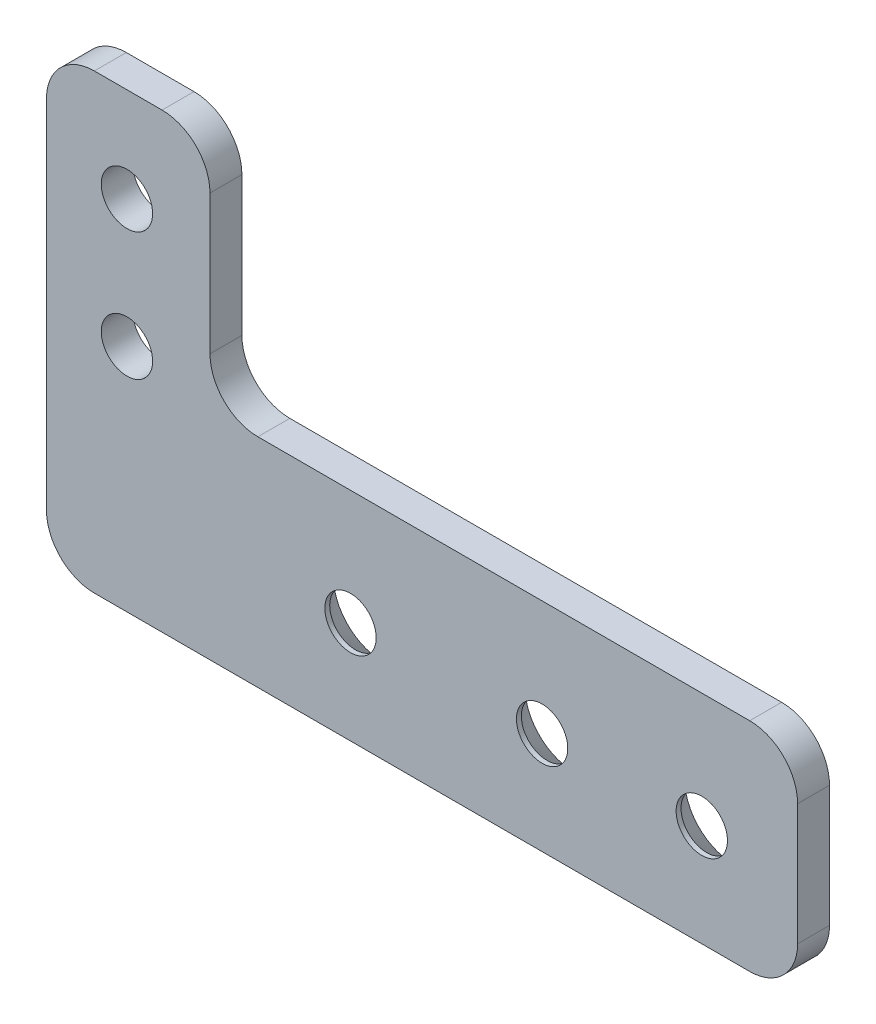
SolidWorks part; units mm, degrees
material "6061-T6 (SS)"
ref_plane "Front Plane" through (0, 0, 0) normal (0, 0, 1) x (1, 0, 0)
ref_plane "Top Plane" through (0, 0, 0) normal (0, 1, 0) x (1, 0, 0)
ref_plane "Right Plane" through (0, 0, 0) normal (1, 0, 0) x (0, 0, -1)
sketch "Sketch1" plane through (0, 0, 0) normal (0, 0, 1) x (1, 0, 0)
  line L0 (41.275, -11.049) -> (-33.401, -11.049) construction
  line L1 (-41.275, -23.749) -> (41.275, -23.749)
  line L2 (-41.275, -23.749) -> (-41.275, 23.749)
  line L3 (-41.275, 23.749) -> (41.275, 23.749)
  line L4 (41.275, -23.749) -> (41.275, 23.749)
  line L5 (-41.275, -23.749) -> (41.275, 23.749) construction
  line L6 (-41.275, 23.749) -> (41.275, -23.749) construction
  line L7 (41.275, 23.749) -> (-17.145, 23.749)
  line L8 (41.275, 23.749) -> (41.275, 0.381)
  line L9 (41.275, 0.381) -> (-17.145, 0.381)
  line L10 (-17.145, 23.749) -> (-17.145, 0.381)
  line L11 (-41.275, -23.749) -> (-33.401, -23.749)
  line L12 (-41.275, -23.749) -> (-41.275, 23.749)
  line L13 (-41.275, 23.749) -> (-33.401, 23.749)
  line L14 (-33.401, -23.749) -> (-33.401, 23.749)
  line L15 (-33.401, -23.749) -> (41.275, -23.749)
  line L16 (-33.401, -23.749) -> (-33.401, -21.209)
  line L17 (-33.401, -21.209) -> (41.275, -21.209)
  line L18 (41.275, -23.749) -> (41.275, -21.209)
  line L19 (-33.401, 23.876) -> (-17.145, 23.876) construction
  circle A0 centre (-25.4, -11.049) radius 2.5527
  circle A1 centre (-25.4, 1.651) radius 2.5527
  circle A2 centre (-25.4, 14.351) radius 2.5527
  point P0 (0, 0)
  point P22 (31.75, -11.049)
  point P23 (-3.175, -11.049)
  point P24 (15.875, -11.049)
  point P25 (0, 0)
  dimension "D7" = 5.1054
  dimension "D1" = 82.55
  dimension "D2" = 47.498
  dimension "D3" = 24.13
  dimension "D4" = 24.13
  dimension "D5" = 7.874
  dimension "D6" = 47.498
  dimension "D8" = 22.225
  dimension "D9" = 12.7
  dimension "D10" = 12.7
  dimension "D11" = 12.7
  dimension "D12" = 9.525
  dimension "D13" = 57.15
  dimension "D14" = 15.875
  dimension "D15" = 15.875
  dimension "D16" = 2.54
extrude "Boss-Extrude1" add sketch "Sketch1" along normal blind 3.175 contours L14 L17 L4 L9 L10 L3 A2 A1 A0 | A0 region at (-0.8769, -6.375, 0) region at (-25.4, -11.049, 0)
fillet "Fillet1" radius 4.7625 6 edges at (-33.401, 23.749, 1.5875) (-17.145, 23.749, 1.5875) (-17.145, 0.381, 1.5875) (41.275, 0.381, 1.5875) (41.275, -21.209, 1.5875) (-33.401, -21.209, 1.5875)
hole_wizard "CSK for #10 Flat Head Machine Screw3" positions "Sketch6" profile "Sketch7" countersink size "#10" standard "ANSI Inch" end condition through all
sketch "Sketch6" plane through (0, 0, 0) normal (0, 0, -1) x (-1, 0, 0)
  point P0 (-31.75, -11.049)
  point P3 (-15.875, -11.049)
  point P6 (3.175, -11.049)
sketch "Sketch7" plane through (31.75, -11.049, 0) normal (1, 0, 0) x (0, 1, 0)
  line L0 (0, 0) -> (0, 3.175)
  line L1 (0, 3.175) -> (2.5527, 3.175)
  line L2 (2.5527, 3.175) -> (2.5527, 2.6882)
  line L3 (2.5527, 2.6882) -> (4.8895, 0)
  line L5 (4.8895, 0) -> (0, 0)
  line L6 (-2.5527, 2.6882) -> (-4.8895, 0) construction
  line L11 (0, -6.35) -> (0, 107.95) construction
  dimension "Thru Hole Dia." = 5.1054
  dimension "Thru Hole Depth" = 3.175
  dimension "Near C'Sink Dia." = 9.779
  dimension "Near C'Sink Angle" = 82
